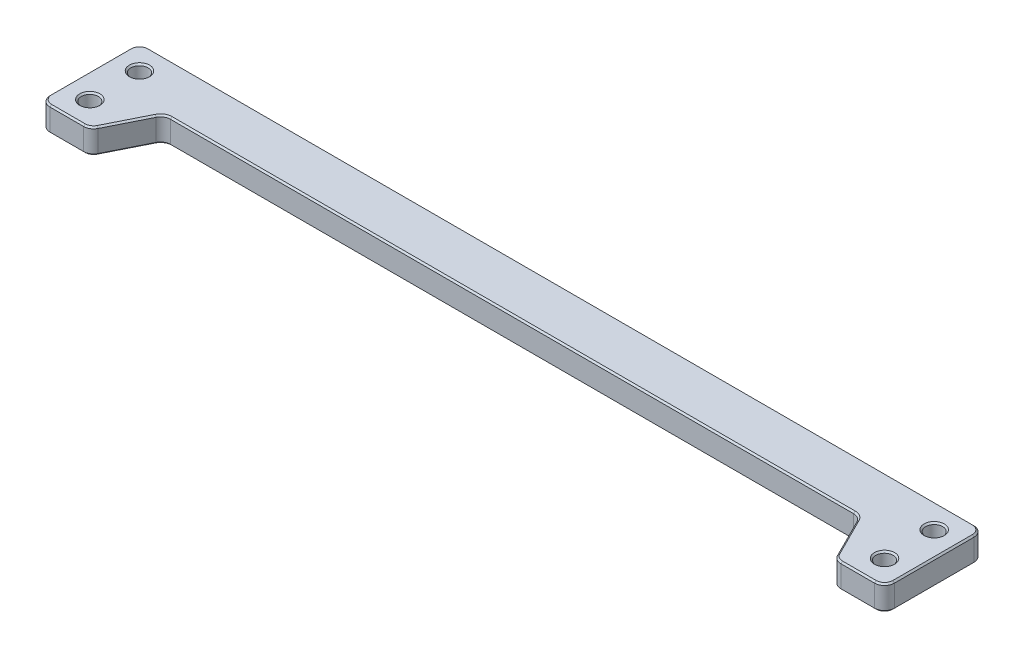
SolidWorks part; units mm, degrees
ref_plane "Front Plane" through (0, 0, 0) normal (0, 0, 1) x (1, 0, 0)
ref_plane "Top Plane" through (0, 0, 0) normal (0, 1, 0) x (1, 0, 0)
ref_plane "Right Plane" through (0, 0, 0) normal (1, 0, 0) x (0, 0, -1)
sketch "Sketch1" plane through (0, 0, 0) normal (0, 1, 0) x (1, 0, 0)
  line L0 (-3.81, 6.35) -> (207.01, 6.35)
  line L1 (209.55, 3.81) -> (209.55, -16.51)
  line L2 (207.01, -19.05) -> (198.4198, -19.05)
  line L3 (196.148, -17.6459) -> (191.202, -7.7541)
  line L4 (188.9302, -6.35) -> (14.2698, -6.35)
  line L5 (11.998, -7.7541) -> (7.052, -17.6459)
  line L6 (4.7802, -19.05) -> (-3.81, -19.05)
  line L7 (-6.35, -16.51) -> (-6.35, 3.81)
  circle A0 centre (0, 0) radius 2.1828
  circle A1 centre (0, -12.7) radius 2.1828
  circle A2 centre (203.2, 0) radius 2.1828
  circle A3 centre (203.2, -12.7) radius 2.1828
  arc A4 (207.01, 6.35) -> (209.55, 3.81) centre (207.01, 3.81) cw
  arc A5 (209.55, -16.51) -> (207.01, -19.05) centre (207.01, -16.51) cw
  arc A6 (198.4198, -19.05) -> (196.148, -17.6459) centre (198.4198, -16.51) cw
  arc A7 (191.202, -7.7541) -> (188.9302, -6.35) centre (188.9302, -8.89) ccw
  arc A8 (-3.81, 6.35) -> (-6.35, 3.81) centre (-3.81, 3.81) ccw
  arc A9 (14.2698, -6.35) -> (11.998, -7.7541) centre (14.2698, -8.89) ccw
  arc A10 (7.052, -17.6459) -> (4.7802, -19.05) centre (4.7802, -16.51) cw
  arc A11 (-3.81, -19.05) -> (-6.35, -16.51) centre (-3.81, -16.51) cw
  point P15 (0, 0)
  point P24 (196.85, -19.05)
  point P27 (190.5, -6.35)
  point P32 (12.7, -6.35)
  point P35 (6.35, -19.05)
  point P38 (-6.35, -19.05)
  dimension "D2" = 4.3656
  dimension "D3" = 4.3656
  dimension "D4" = 4.3656
  dimension "D5" = 4.3656
  dimension "D18" = 2.54
  dimension "D1" = 203.2
  dimension "D6" = 12.7
  dimension "D7" = 12.7
  dimension "D8" = 6.35
  dimension "D9" = 6.35
  dimension "D10" = 6.35
  dimension "D11" = 6.35
  dimension "D12" = 6.35
  dimension "D13" = 6.35
  dimension "D14" = 12.7
  dimension "D15" = 6.35
  dimension "D16" = 12.7
  dimension "D17" = 6.35
extrude "Boss-Extrude1" add sketch "Sketch1" along normal mid plane 6.35
chamfer "Chamfer1" distance 0.3969 angle 45 40 edges at (203.2, -3.175, 14.8828) (0, -3.175, 14.8828) (101.6, -3.175, -6.35) (-5.6061, -3.175, -5.6061) (-6.35, -3.175, 6.35) (-5.6061, -3.175, 18.3061) (0.4851, -3.175, 19.05) (6.1156, -3.175, 18.6707) (9.525, -3.175, 12.7) (12.9344, -3.175, 6.7293) (101.6, -3.175, 6.35) (190.2656, -3.175, 6.7293) (193.675, -3.175, 12.7) (197.0844, -3.175, 18.6707) (202.7149, -3.175, 19.05) (208.8061, -3.175, 18.3061) (209.55, -3.175, 6.35) (208.8061, -3.175, -5.6061) (0, -3.175, 2.1828) (203.2, -3.175, 2.1828) (203.2, 3.175, 14.8828) (203.2, 3.175, 2.1828) (0, 3.175, 14.8828) (0, 3.175, 2.1828) (209.55, 3.175, 6.35) (208.8061, 3.175, 18.3061) (202.7149, 3.175, 19.05) (197.0844, 3.175, 18.6707) (193.675, 3.175, 12.7) (190.2656, 3.175, 6.7293) (101.6, 3.175, 6.35) (12.9344, 3.175, 6.7293) (9.525, 3.175, 12.7) (6.1156, 3.175, 18.6707) (0.4851, 3.175, 19.05) (-5.6061, 3.175, 18.3061) (-6.35, 3.175, 6.35) (-5.6061, 3.175, -5.6061) (101.6, 3.175, -6.35) (208.8061, 3.175, -5.6061)
